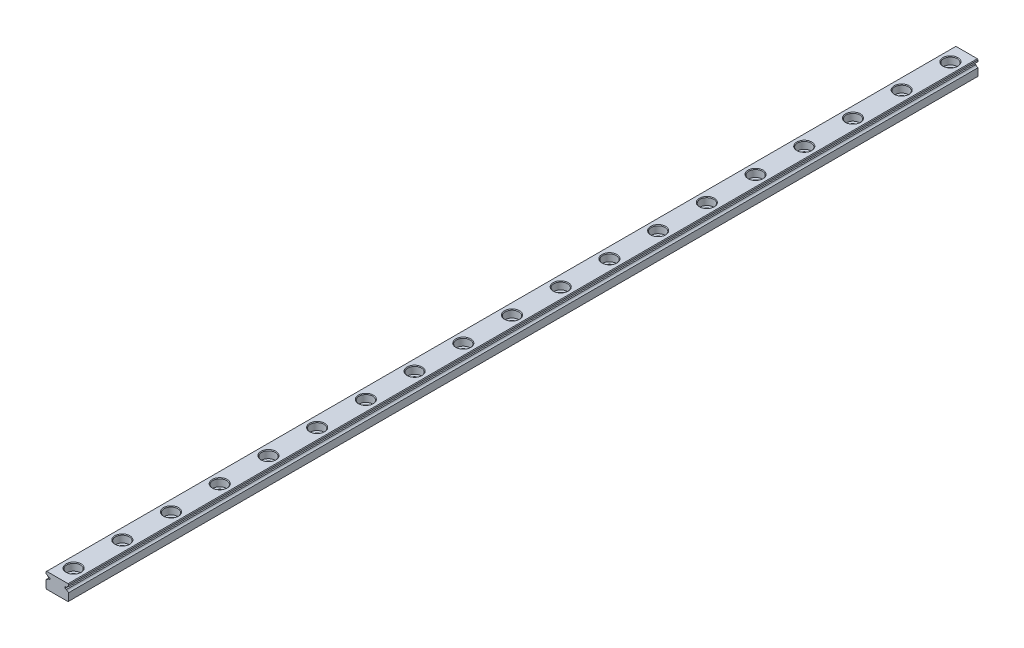
SolidWorks part; units mm, degrees
ref_plane "Спереди" through (0, 0, 0) normal (0, 0, 1) x (1, 0, 0)
ref_plane "Сверху" through (0, 0, 0) normal (0, 1, 0) x (1, 0, 0)
ref_plane "Справа" through (0, 0, 0) normal (1, 0, 0) x (0, 0, -1)
sketch "Sketch1" plane through (0, 0, 0) normal (0, 0, 1) x (1, 0, 0)
  line L0 (0, 0) -> (0, 4.3706) construction
  line L1 (-3.3, -2.4) -> (3.3, -2.4)
  line L2 (-3.5, -2.2) -> (-3.5, 0.1063)
  line L3 (-3.3, 2.4) -> (3.3, 2.4)
  line L4 (3.5, -2.2) -> (3.5, 0.1063)
  line L5 (-3.5, -2.4) -> (3.5, 2.4) construction
  line L6 (-3.5, 2.4) -> (3.5, -2.4) construction
  line L7 (-3.5, 1.6937) -> (-3.5, 2.2)
  line L8 (3.5, 1.6937) -> (3.5, 2.2)
  line L9 (-3.5, -2.2) -> (-3.3, -2.4)
  line L10 (3.3, -2.4) -> (3.5, -2.2)
  line L11 (3.3, 2.4) -> (3.5, 2.2)
  line L12 (-3.5, 2.2) -> (-3.3, 2.4)
  line L13 (2.8401, 0.65) -> (2.3401, 0.65)
  line L14 (-2.8401, 0.65) -> (-2.3401, 0.65)
  line L15 (2.3401, 0.65) -> (2.3401, 1.15)
  line L16 (-2.8401, 1.15) -> (-2.3401, 1.15)
  line L17 (-2.3401, 0.65) -> (-2.3401, 1.15)
  line L18 (2.8401, 1.15) -> (2.3401, 1.15)
  arc A0 (-3.5, 1.6937) -> (-2.8401, 1.15) centre (-3.6, 0.9) cw
  arc A1 (3.5, 1.6937) -> (2.8401, 1.15) centre (3.6, 0.9) ccw
  arc A2 (-2.8401, 0.65) -> (-3.5, 0.1063) centre (-3.6, 0.9) cw
  arc A3 (2.8401, 0.65) -> (3.5, 0.1063) centre (3.6, 0.9) ccw
  point P0 (0, 0)
  dimension "D4" = 0.8
  dimension "D5" = 0.1
  dimension "D1" = 7
  dimension "D2" = 4.8
  dimension "D3" = 1.5
  dimension "D6" = 0.5
  dimension "D7" = 0.5
extrude "Extrude1" add sketch "Sketch1" along normal blind 280
sketch "Sketch2" plane through (0, 2.4, 0) normal (0, 1, 0) x (1, 0, 0)
  line L0 (0, 0) -> (0, -5) construction
  circle A0 centre (0, -5) radius 1.2
  circle A1 centre (0, -5) radius 2.1
  dimension "D1" = 2.4
  dimension "D2" = 4.2
  dimension "D3" = 5
extrude "Extrude2" cut sketch "Sketch2" against normal up to next contours A0 region at (0, 2.4, 5)
extrude "Extrude4" cut sketch "Sketch" against normal blind 2.3
sketch "Sketch" plane through (0, 2.4, 0) normal (0, 1, 0) x (1, 0, 0) same geometry as "Sketch2"
chamfer "Chamfer1" distance 0.2 angle 45 2 edges at (0, -2.4, 6.2) (0, 2.4, 7.1)
pattern_linear "LPattern1" count 19 spacing 15 along (0, 0, 1) of "Extrude4", "Chamfer1", "Extrude2"
